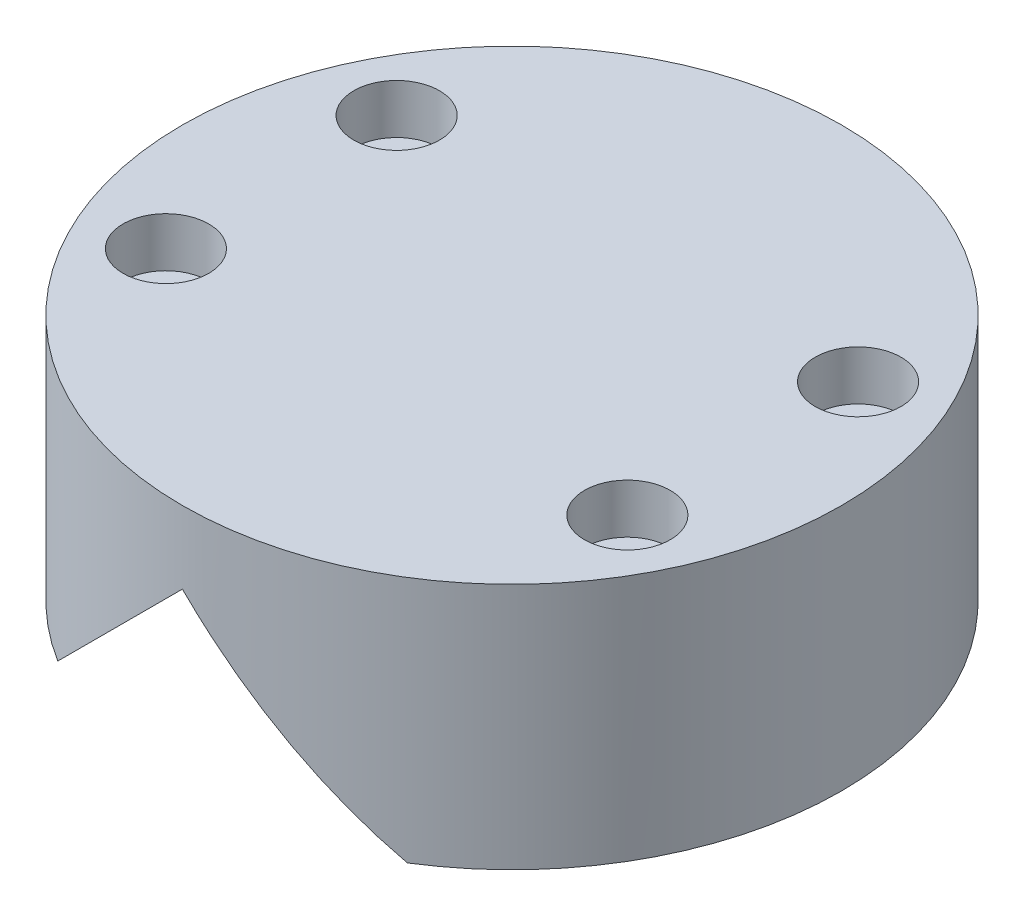
SolidWorks part; units mm, degrees
ref_plane "Front Plane" through (0, 0, 0) normal (0, 0, 1) x (1, 0, 0)
ref_plane "Top Plane" through (0, 0, 0) normal (0, 1, 0) x (1, 0, 0)
ref_plane "Right Plane" through (0, 0, 0) normal (1, 0, 0) x (0, 0, -1)
sketch "Sketch1" plane through (0, 0, 0) normal (0, 1, 0) x (1, 0, 0)
  circle A0 centre (0, 0) radius 20
  dimension "D1" = 40
extrude "Boss-Extrude1" add sketch "Sketch1" along normal blind 15
sketch "Sketch2" plane through (0, 0, 0) normal (0, 0, 1) x (1, 0, 0)
  line L0 (-10.6066, 0) -> (10.6066, 0)
  line L1 (-20, 0) -> (20, 0) construction
  line L2 (10.6066, 0) -> (0, 10.6066)
  line L3 (0, 10.6066) -> (-10.6066, 0)
  dimension "D1" = 15
  dimension "D2" = 15
  dimension "D3" = 45
  dimension "D4" = 0
extrude "Cut-Extrude1" cut sketch "Sketch2" against normal blind 25 and the other way blind 25
sketch "Sketch3" plane through (0, 0, 0) normal (0, -1, 0) x (-1, 0, 0)
  circle A0 centre (14, -7) radius 1.5
  circle A1 centre (14, 7) radius 1.5
  circle A2 centre (-14, -7) radius 1.5
  circle A3 centre (-14, 7) radius 1.5
  point P8 (0, 0)
  dimension "D1" = 3
  dimension "D2" = 3
  dimension "D3" = 3
  dimension "D4" = 3
  dimension "D5" = 14
  dimension "D6" = 14
  dimension "D7" = 7
  dimension "D8" = 14
  dimension "D9" = 14
  dimension "D10" = 28
  dimension "D11" = 7
extrude "Cut-Extrude2" cut sketch "Sketch3" against normal up to next
sketch "Sketch4" plane through (0, 15, 0) normal (0, 1, 0) x (1, 0, 0)
  circle A0 centre (-14, 7) radius 2.6
  circle A1 centre (-14, -7) radius 2.6
  circle A2 centre (14, 7) radius 2.6
  circle A3 centre (14, -7) radius 2.6
  dimension "D1" = 5.2
  dimension "D2" = 5.2
  dimension "D3" = 5.2
  dimension "D4" = 5.2
extrude "Cut-Extrude3" cut sketch "Sketch4" against normal blind 3
